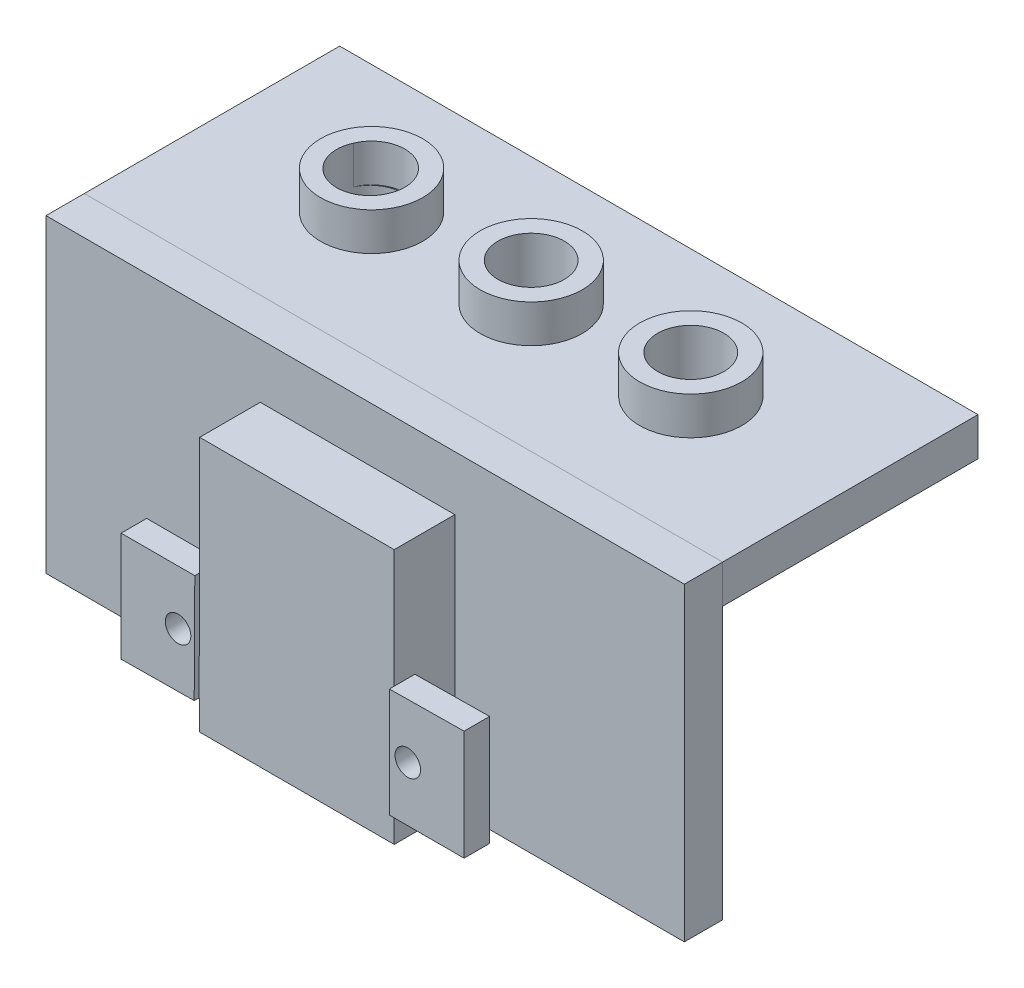
SolidWorks part; units mm, degrees
ref_plane "Front Plane" through (0, 0, 0) normal (0, 0, 1) x (1, 0, 0)
ref_plane "Top Plane" through (0, 0, 0) normal (0, 1, 0) x (1, 0, 0)
ref_plane "Right Plane" through (0, 0, 0) normal (1, 0, 0) x (0, 0, -1)
sketch "Sketch1" plane through (0, 0, 0) normal (0, 1, 0) x (1, 0, 0)
  line L1 (-25, -10) -> (25, -10)
  line L2 (-25, -10) -> (-25, 10)
  line L3 (-25, 10) -> (25, 10)
  line L4 (25, -10) -> (25, 10)
  line L5 (-25, -10) -> (25, 10) construction
  line L6 (-25, 10) -> (25, -10) construction
  point P0 (0, 0)
extrude "Boss-Extrude2" add sketch "Sketch1" along normal blind 3
sketch "Sketch3" plane through (0, 3, 0) normal (0, 1, 0) x (1, 0, 0)
  circle A0 centre (0, 0) radius 4
  circle A1 centre (-12.5, 0) radius 4
  circle A2 centre (12.5, 0) radius 4
extrude "Boss-Extrude3" add sketch "Sketch3" along normal blind 6.27
sketch "Sketch4" plane through (0, 9.27, 0) normal (0, 1, 0) x (1, 0, 0)
  circle A0 centre (0, 0) radius 2.6
  circle A1 centre (-12.5, 0) radius 2.6
  circle A2 centre (12.5, 0) radius 2.6
extrude "Cut-Extrude1" cut sketch "Sketch4" against normal through all both and the other way through all
sketch "Sketch5" plane through (-25, 0, 0) normal (-1, 0, 0) x (0, 0, 1)
  line L0 (10, 3) -> (10, 5.3)
  line L1 (10, 3) -> (-10, 3)
  line L2 (-10, 3) -> (-10, 5.3)
  line L3 (-10, 5.3) -> (10, 5.3)
extrude "Boss-Extrude4" add sketch "Sketch5" against normal blind 50
sketch "Sketch6" plane through (-25, 0, 0) normal (-1, 0, 0) x (0, 0, 1)
  line L0 (-10, 0) -> (-10, 2.65)
  line L1 (-10, 5.3) -> (-10, 0) construction
  line L2 (-10, 2.65) -> (10, 2.65)
  line L3 (10, 5.3) -> (10, 0) construction
  line L4 (10, 2.65) -> (10, 0)
  line L5 (10, 0) -> (-10, 0)
extrude "Cut-Extrude2" cut sketch "Sketch6" against normal through all both and the other way through all
sketch "Sketch7" plane through (0, 2.65, 0) normal (0, -1, 0) x (1, 0, 0)
  circle A0 centre (-12.5, 0) radius 2.6
  circle A1 centre (0, 0) radius 2.6
  circle A2 centre (12.5, 0) radius 2.6
extrude "Cut-Extrude3" cut sketch "Sketch7" against normal through all both and the other way through all
sketch "Sketch8" plane through (-25, 0, 0) normal (-1, 0, 0) x (0, 0, 1)
  line L0 (-10, 5.3) -> (-10, 6.3)
  line L1 (-10, 6.3) -> (10.0042, 6.3)
  line L2 (10.0042, 6.3) -> (10, 2.65)
  line L3 (10, 2.65) -> (-10, 2.65)
  line L4 (-10, 2.65) -> (-10, 6.3)
  line M5 (-10, 5.3) -> (-10, 2.65)
  line M6 (-10, 2.65) -> (10, 2.65)
  line M7 (10, 2.65) -> (10, 5.3)
  line M8 (10, 5.3) -> (-10, 5.3)
extrude "Boss-Extrude5" add sketch "Sketch8" against normal blind 50 contours L2 L1 L0 M8 M7 | M8 M5 M6 M7 region at (-25, 3.975, 0) region at (-25, 5.7997, 0.0038)
sketch "Sketch10" plane through (0, 6.3, 0) normal (0, 1, 0) x (1, 0, 0)
  circle A0 centre (12.5, 0) radius 2.6
  circle A1 centre (0, 0) radius 2.6
  circle A2 centre (-12.5425, -0.0968) radius 2.6
extrude "Cut-Extrude4" cut sketch "Sketch10" against normal through all both and the other way through all
sketch "Sketch11" plane through (-25, 0, 0) normal (-1, 0, 0) x (0, 0, 1)
  line L0 (10, 2.65) -> (10.0007, 3.3)
  line L1 (10.0042, 6.3) -> (10, 2.65) construction
  line L2 (10.0007, 3.3) -> (-10, 3.3)
  line L3 (-10, 6.3) -> (-10, 2.65) construction
  line L4 (-10, 3.3) -> (-10, 2.65)
  line L5 (-10, 2.65) -> (10, 2.65)
extrude "Cut-Extrude5" cut sketch "Sketch11" against normal through all both and the other way through all
sketch "Sketch12" plane through (-25, 0, 0) normal (-1, 0, 0) x (0, 0, 1)
  line L0 (10.0042, 6.3) -> (13.0042, 6.3)
  line L1 (13.0042, 6.3) -> (13.0042, -17.9693)
  line L2 (13.0042, -17.9693) -> (10.0007, -17.9693)
  line L3 (10.0007, -17.9693) -> (10.0042, 6.3)
extrude "Boss-Extrude6" add sketch "Sketch12" against normal blind 50 separate body
sketch "Sketch13" plane through (0, 0, 13.0042) normal (0, 0, 1) x (1, 0, 0)
  line L0 (-8.2146, 2.0307) -> (-8.2146, -7.1666)
  line L1 (-7.9836, -7.1666) -> (-13.9836, -7.1666)
  line L2 (25, -17.9693) -> (-25, -17.9693) construction
  line L4 (7.0245, -4.2347) -> (7.0245, 2.0307)
  line L5 (7.0245, 2.0307) -> (7.0245, -7.2343)
  line L6 (7.0245, -17.9693) -> (-8.2146, -17.9693)
  line L7 (-8.2146, -17.9693) -> (-8.2146, -15.717)
  line L8 (-8.2146, 2.0307) -> (7.0245, 2.0307)
  line L9 (-13.9836, -7.1666) -> (-13.9836, -15.717)
  line L10 (-8.2146, -17.9693) -> (7.0245, -17.9693)
  line L11 (-8.1167, -15.717) -> (-13.9836, -15.717)
  line L12 (6.8787, -15.7848) -> (12.8787, -15.7848)
  line L13 (12.8787, -15.7848) -> (12.8787, -7.1666)
  line L14 (12.8787, -7.1666) -> (7.0118, -7.2344)
  line L15 (7.0245, -15.7848) -> (7.0245, -17.9693)
  line L16 (-8.2146, -15.717) -> (-8.2146, -17.9693)
  line L17 (-8.2146, -7.1666) -> (-8.2146, 2.0307)
  line M2 (-25, -17.9693) -> (25, -17.9693)
extrude "Boss-Extrude9" add sketch "Sketch13" along normal blind 4.75 contours L15 L12 L13 L14 L5 L4 L8 L0 L1 L9 L11 L7 M2 region at (-0.5652, -8.8308, 13.0042)
sketch "Sketch19" plane through (0, 0, 17.7542) normal (0, 0, 1) x (1, 0, 0)
  line L0 (-8.2146, -7.1666) -> (-13.9836, -7.1666)
  line L1 (-13.9836, -7.1666) -> (-13.9836, -15.717)
  line L2 (-13.9836, -15.717) -> (-8.2614, -15.6647)
  line L3 (-6.5198, -15.6726) -> (-10.0031, -15.6569) construction
  line L4 (-8.2614, -15.6647) -> (-8.2146, -7.1666)
  line L5 (7.0245, -7.2343) -> (7.0245, -15.7848)
  line L6 (7.0245, -15.7848) -> (12.8787, -15.7848)
  line L7 (12.8787, -15.7848) -> (12.8787, -7.1666)
  line L8 (12.8787, -7.1666) -> (7.0245, -7.2343)
extrude "Boss-Extrude10" add sketch "Sketch19" along normal blind 0.38
sketch "Sketch20" plane through (0, 0, 18.1342) normal (0, 0, 1) x (1, 0, 0)
  circle A0 centre (-9.5253, -11.4222) radius 0.9999
  circle A1 centre (8.4692, -11.5036) radius 0.9999
extrude "Cut-Extrude6" cut sketch "Sketch20" against normal through all both and the other way through all
sketch "Sketch21" plane through (0, -15.717, 0) normal (0, -1, 0) x (1, 0, 0)
  line L1 (-13.9836, 17.7542) -> (-13.9836, 13.0042) construction
  line L2 (-13.9836, 16.1342) -> (-8.2146, 16.1342)
  line L3 (-8.2146, 17.7542) -> (-8.2146, 13.0042) construction
  line L4 (-8.2146, 16.1342) -> (-8.2146, 13.0042)
  line L5 (-8.2146, 13.0042) -> (-13.9836, 13.0042)
  line L6 (-13.9836, 13.0042) -> (-13.9836, 16.1342)
  line L7 (7.0245, 17.7542) -> (7.0245, 13.0042) construction
  line L8 (7.0245, 16.1342) -> (12.8787, 16.1342)
  line L9 (12.8787, 18.1342) -> (12.8787, 13.0042) construction
  line L10 (12.8787, 16.1342) -> (12.8787, 13.0042)
  line L11 (12.8787, 13.0042) -> (7.0245, 13.0042)
  line L12 (25, 13.0042) -> (7.0245, 13.0042) construction
  line L13 (7.0245, 13.0042) -> (7.0245, 16.1342)
extrude "Cut-Extrude7" cut sketch "Sketch21" against normal through all both and the other way through all contours L8 L10 L11 L13 | L2 L4 L5 L6
